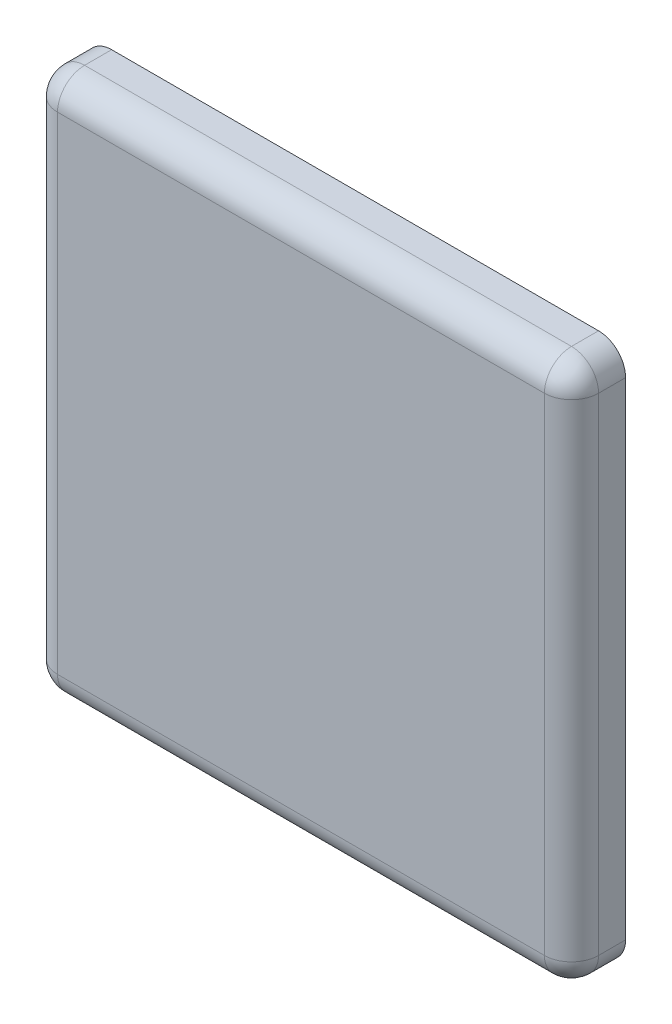
SolidWorks part; units mm, degrees
ref_plane "Top" through (0, 0, 0) normal (0, 0, 1) x (1, 0, 0)
ref_plane "Front" through (0, 0, 0) normal (0, 1, 0) x (1, 0, 0)
ref_plane "Right" through (0, 0, 0) normal (1, 0, 0) x (0, 0, -1)
sketch "Cap Sketch" plane through (0, 0, 0) normal (0, 0, 1) x (1, 0, 0)
  line L1 (-10, -10) -> (10, -10)
  line L2 (-10, -10) -> (-10, 10)
  line L3 (-10, 10) -> (10, 10)
  line L4 (10, -10) -> (10, 10)
  line L5 (-10, -10) -> (10, 10) construction
  line L6 (-10, 10) -> (10, -10) construction
  point P0 (0, 0)
  dimension "Width" = 20
  dimension "Length" = 20
extrude "Extrude Thickness" add sketch "Cap Sketch" along normal blind 2
fillet "Corner Fillets" radius 1 4 edges at (-10, -10, 1) (-10, 10, 1) (10, 10, 1) (10, -10, 1)
fillet "Top Edge Fillet" radius 1 8 edges at (-9.7071, 9.7071, 2) (0, 10, 2) (9.7071, 9.7071, 2) (10, 0, 2) (9.7071, -9.7071, 2) (0, -10, 2) (-9.7071, -9.7071, 2) (-10, 0, 2)
equation "\"M8 Close Fit Hole\"= 8.4"
